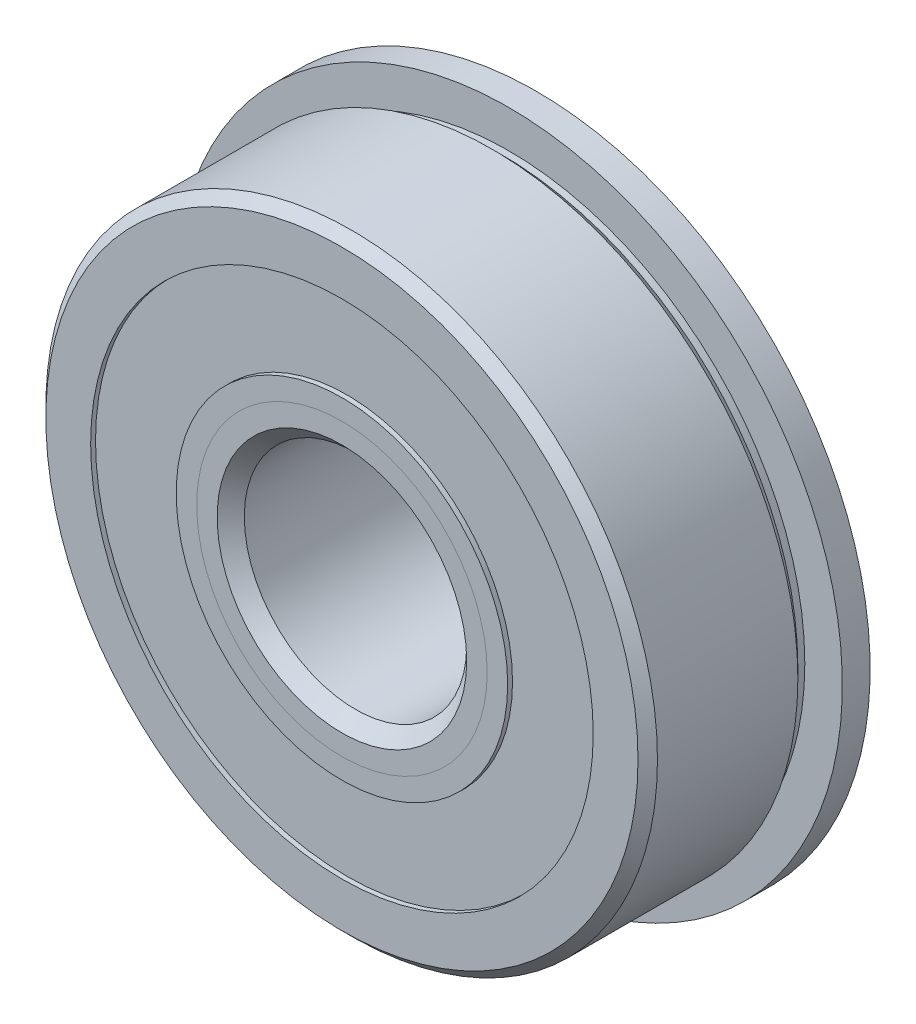
SolidWorks part; units mm, degrees
ref_plane "Front Plane" through (0, 0, 0) normal (0, 0, 1) x (1, 0, 0)
ref_plane "Top Plane" through (0, 0, 0) normal (0, 1, 0) x (1, 0, 0)
ref_plane "Right Plane" through (0, 0, 0) normal (1, 0, 0) x (0, 0, -1)
sketch "Sketch1" plane through (0, 0, 0) normal (1, 0, 0) x (0, 0, -1)
  line L0 (-5.5562, 0) -> (5.5562, 0) construction
  line L1 (0, 17.4625) -> (0, -17.4625) construction
  line L2 (5.0006, 17.4625) -> (-5.0006, 17.4625) construction
  line L3 (-5.0006, 17.4625) -> (-5.5563, 16.9069) construction
  line L4 (-5.5563, 16.9069) -> (-5.5563, 14.3486) construction
  line L5 (-5.5563, 14.3486) -> (-3.175, 14.3486) construction
  line L6 (5.5563, 14.3486) -> (3.175, 14.3486) construction
  line L7 (5.5563, 16.9069) -> (5.5563, 14.3486) construction
  line L8 (5.0006, 17.4625) -> (5.5563, 16.9069) construction
  line L9 (0, 17.4625) -> (0, 11.9062) construction
  line L10 (0, 11.9062) -> (0, 6.35) construction
  line L11 (5.5562, 0) -> (7.1437, 0) construction
  line L12 (7.1437, 11.5062) -> (7.1438, -11.5062) construction
  line L13 (7.1438, -19.05) -> (7.1437, 19.05) construction
  arc A0 (-3.175, 14.3486) -> (3.175, 14.3486) centre (0, 11.9062) cw construction
  point P14 (0, 6.35)
  point P20 (7.1437, 0)
  point P23 (7.1437, 0)
  dimension "OD" = 34.925
  dimension "D1" = 45
  dimension "D2" = 0.5556
  dimension "D3" = 6.35
  dimension "D4" = 2.4423
  dimension "Width" = 11.1125
  dimension "Total Wd" = 12.7
  dimension "Shaft Dia" = 12.7
  dimension "Inner Ring OD" = 23.0124
  dimension "Flange OD" = 38.1
sketch "Sketch11" plane through (0, 0, 0) normal (0, 0, 1) x (1, 0, 0)
  circle A0 centre (0, 0) radius 6.35 construction
  dimension "Shaft Dia" = 12.7
sketch "Sketch8" plane through (0, 0, 0) normal (1, 0, 0) x (0, 0, -1)
  line L0 (5.0006, 17.4625) -> (-5.0006, 17.4625) construction
  line L1 (5.0006, 17.4625) -> (5.5563, 16.9069) construction
  line L2 (5.5563, 16.9069) -> (5.5563, 14.3486) construction
  line L3 (5.5563, 14.3486) -> (3.175, 14.3486) construction
  line L4 (-5.5563, 14.3486) -> (-3.175, 14.3486) construction
  line L5 (-5.5563, 16.9069) -> (-5.5563, 14.3486) construction
  line L6 (-5.0006, 17.4625) -> (-5.5563, 16.9069) construction
  line L7 (5.0006, 17.4625) -> (-5.0006, 17.4625)
  line L8 (5.0006, 17.4625) -> (5.5563, 16.9069)
  line L9 (5.5563, 16.9069) -> (5.5563, 14.3486)
  line L10 (5.5563, 14.3486) -> (3.175, 14.3486)
  line L11 (-5.5563, 14.3486) -> (-3.175, 14.3486)
  line L12 (-5.5563, 16.9069) -> (-5.5563, 14.3486)
  line L13 (-5.0006, 17.4625) -> (-5.5563, 16.9069)
  arc A0 (3.175, 14.3486) -> (-3.175, 14.3486) centre (0, 11.9062) ccw construction
  arc A1 (3.175, 14.3486) -> (-3.175, 14.3486) centre (0, 11.9062) ccw
revolve "Revolve7" add sketch "Sketch8" angle 360 about L0 region at (0, 16.1229, 0)
sketch "Sketch2" plane through (0, 0, 0) normal (1, 0, 0) x (0, 0, -1)
  line L0 (-5.5563, 9.4639) -> (-3.175, 9.4639)
  line L2 (-5.5563, 9.4639) -> (-5.5563, 8.2946)
  line L3 (-5.5563, 8.2946) -> (-4.3869, 7.1253)
  line L4 (-4.3869, 7.1253) -> (0, 7.1253)
  line L5 (0, 17.4625) -> (0, -17.4625) construction
  line L6 (0, 7.1253) -> (0, 7.9006)
  line L7 (0, 7.9006) -> (0, 6.35) construction
  line L8 (-5.5563, 9.4639) -> (-5.5563, 7.1253) construction
  line L9 (-5.5563, 7.1253) -> (-4.3869, 7.1253) construction
  line L10 (-5.5563, 16.9069) -> (-5.5563, -16.9069) construction
  arc A0 (-3.175, 9.4639) -> (0, 7.9006) centre (0, 11.9062) ccw
  arc A1 (3.175, 14.3486) -> (-3.175, 14.3486) centre (0, 11.9062) ccw construction
  circle A2 centre (0, 11.9062) radius 4.0057 construction
  dimension "D1" = 45
revolve "Revolve2" add sketch "Sketch2" angle 360 about L0
sketch "Sketch3" plane through (0, 0, 0) normal (1, 0, 0) x (0, 0, -1)
  line L0 (-5.5563, 8.2946) -> (-4.3869, 7.1253)
  line L1 (-4.3869, 7.1253) -> (0, 7.1253)
  line L2 (0, 7.1253) -> (0, 7.9006)
  line L3 (-5.5563, 8.2946) -> (-5.5563, 7.1253)
  line L4 (-5.5563, 9.4639) -> (-5.5563, 7.1253) construction
  line L5 (-5.5563, 7.1253) -> (-4.781, 6.35)
  line L6 (-4.781, 6.35) -> (6.5881, 6.35)
  line L7 (10.4392, 0) -> (-10.4392, 0) construction
  line L8 (6.5881, 6.35) -> (7.1438, 6.9056)
  line L10 (7.1438, 6.9056) -> (7.1437, 11.5062)
  line L11 (7.1437, 11.5062) -> (3.9857, 11.5062)
  line L13 (5.0006, 17.4625) -> (5.5563, 16.9069) construction
  circle A0 centre (0, 11.9062) radius 4.0057 construction
  arc A1 (3.9857, 11.5062) -> (0, 7.9006) centre (0, 11.9062) cw
  point P18 (0, 0)
  dimension "Inner Ring OD" = 23.0124
revolve "Revolve3" add sketch "Sketch3" angle 360 about L0
sketch "Sketch5" plane through (0, 0, 0) normal (1, 0, 0) x (0, 0, -1)
  line L0 (5.5563, 16.9069) -> (5.5563, 14.3486) construction
  line L1 (5.5563, 15.6277) -> (3.9688, 15.6277)
  line L2 (5.5563, 15.6277) -> (5.5563, 19.05)
  line L3 (5.5563, 19.05) -> (3.9688, 19.05)
  line L4 (3.9688, 15.6277) -> (3.9688, 19.05)
  line L5 (7.1437, 0) -> (-5.5562, 0) construction
  dimension "Flange OD" = 38.1
  dimension "D1" = 1.5875
revolve "Revolve5" add sketch "Sketch5" angle 360 about L5
sketch "Sketch6" plane through (0, 0, 0) normal (1, 0, 0) x (0, 0, -1)
  line L0 (3.0163, 17.4625) -> (3.5719, 16.9069)
  line L1 (5.0006, 17.4625) -> (-5.0006, 17.4625) construction
  line L2 (3.5719, 16.9069) -> (3.9688, 16.9069)
  line L3 (3.9688, 16.9069) -> (3.9688, 17.4625)
  line L4 (3.9688, 17.4625) -> (3.0163, 17.4625)
  line L5 (5.0006, 17.4625) -> (5.5563, 16.9069) construction
  line L6 (3.9688, 15.6277) -> (3.9688, 19.05) construction
  dimension "D1" = 0.3969
revolve "Cut-Revolve1" cut sketch "Sketch6" angle 360 about L0
sketch "Sketch4" plane through (0, 0, 0) normal (1, 0, 0) x (0, 0, -1)
  line L0 (-4.0057, 11.9062) -> (4.0057, 11.9062)
  circle A1 centre (0, 11.9062) radius 4.0057 construction
  arc A2 (-4.0057, 11.9062) -> (4.0057, 11.9062) centre (0, 11.9062) cw
  arc A3 (3.175, 14.3486) -> (-3.175, 14.3486) centre (0, 11.9062) ccw construction
revolve "Revolve4" add sketch "Sketch4" angle 360 about L0
ref_axis "Axis1" through (0, 0, -5.5562) along (0, 0, 1)
pattern_circular "CirPattern1" count 12 over 360 about axis through (0, 0, 5.5562) along (0, 0, -1) of bodies 104
sketch "Sketch7" plane through (0, 0, 0) normal (1, 0, 0) x (0, 0, -1)
  line L0 (-5.5563, 14.3486) -> (-3.175, 14.3486) construction
  line L1 (-5.2784, 14.3486) -> (-4.0057, 14.3486)
  line L2 (-5.2784, 14.3486) -> (-5.2784, 9.4639)
  line L3 (-5.2784, 9.4639) -> (-4.0057, 9.4639)
  line L4 (-4.0057, 14.3486) -> (-4.0057, 9.4639)
  line L5 (-5.5563, 9.4639) -> (-3.175, 9.4639) construction
  line L6 (-5.0006, 17.4625) -> (-5.5563, 16.9069) construction
  line L7 (5.5563, 14.3486) -> (3.175, 14.3486) construction
  line L8 (5.2784, 14.3486) -> (4.0057, 14.3486)
  line L9 (5.2784, 14.3486) -> (5.2784, 11.5062)
  line L10 (5.2784, 11.5062) -> (4.0057, 11.5062)
  line L11 (4.0057, 14.3486) -> (4.0057, 11.5062)
  line L12 (7.1437, 11.5062) -> (3.9857, 11.5062) construction
  line L13 (5.0006, 17.4625) -> (5.5563, 16.9069) construction
  circle A0 centre (0, 11.9062) radius 4.0057 construction
  point P10 (-5.2784, 17.1847)
  point P21 (5.2784, 17.1847)
revolve "Revolve6" add sketch "Sketch7" angle 360 about L0
sketch "Sketch9" plane through (0, 0, -7.1438) normal (0, 0, -1) x (-1, 0, 0)
  line L0 (0, 11.5062) -> (0, 6.9056) construction
  circle A0 centre (0, 0) radius 6.9056 construction
  circle A1 centre (0, 0) radius 11.5062
  circle A2 centre (0, 0) radius 11.5062 construction
  circle A3 centre (0, 0) radius 6.9056 construction
  circle A4 centre (0, 0) radius 9.2059 construction
  circle A5 centre (0, 0) radius 9.436
  circle A6 centre (0, 0) radius 8.9758
  point P8 (0, 9.2059)
  dimension "D2" = 0.2301
  dimension "D3" = 0.2301
extrude "Cut-Extrude1" cut sketch "Sketch9" against normal blind 0.127
sketch "Sketch10" plane through (0, 0, -5.2784) normal (0, 0, -1) x (-1, 0, 0)
  circle A0 centre (0, 0) radius 11.5062 construction
  circle A1 centre (0, 0) radius 11.5062
  circle A2 centre (0, 0) radius 12.4267
  dimension "D1" = 0.9205
extrude "Cut-Extrude2" cut sketch "Sketch10" against normal blind 0.254
equation "\"D2@Sketch1\" = \"Width@Sketch1\"*.05"
equation "\"D3@Sketch1\"=\"Width@Sketch1\"/1.75"
equation "\"D4@Sketch1\"=(((\"OD@Sketch1\"-\"Width@Sketch1\")/2)/3.25)/1.5"
equation "\"Inner Ring OD@Sketch3\"=\"Inner Ring OD@Sketch1\""
equation "\"Flange OD@Sketch5\"=\"Flange OD@Sketch1\""
equation "\"D1@Sketch10\"=\"Inner Ring OD@Sketch1\"*.04"
equation "\"D2@Sketch9\"=\"Inner Ring OD@Sketch1\"*.01"
equation "\"D3@Sketch9\"=\"Inner Ring OD@Sketch1\"*.01"
equation "\"Shaft Dia@Sketch1\"=\"Shaft Dia@Sketch11\""
